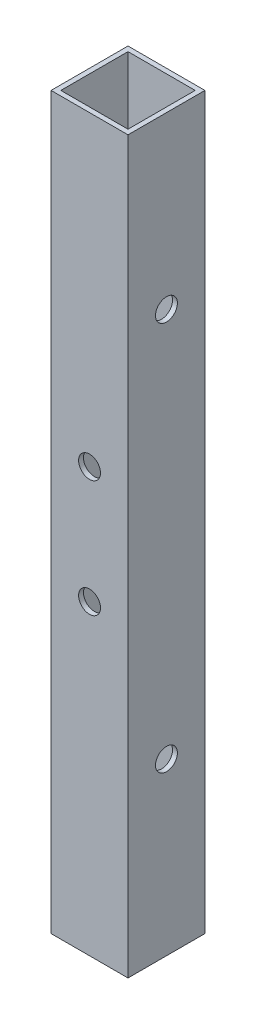
SolidWorks part; units mm, degrees
ref_plane "Front Plane" through (0, 0, 0) normal (0, 0, 1) x (1, 0, 0)
ref_plane "Top Plane" through (0, 0, 0) normal (0, 1, 0) x (1, 0, 0)
ref_plane "Right Plane" through (0, 0, 0) normal (1, 0, 0) x (0, 0, -1)
sketch "Sketch1" plane through (0, 0, 0) normal (0, 1, 0) x (1, 0, 0)
  line L0 (-6.9, -6.9) -> (-6.9, 6.9)
  line L1 (-7.9, -7.9) -> (7.9, -7.9)
  line L2 (-7.9, -7.9) -> (-7.9, 7.9)
  line L3 (-7.9, 7.9) -> (7.9, 7.9)
  line L4 (7.9, -7.9) -> (7.9, 7.9)
  line L5 (-7.9, -7.9) -> (7.9, 7.9) construction
  line L6 (-7.9, 7.9) -> (7.9, -7.9) construction
  line L7 (-6.9, 6.9) -> (6.9, 6.9)
  line L8 (6.9, -6.9) -> (6.9, 6.9)
  line L9 (-6.9, -6.9) -> (6.9, -6.9)
  point P0 (0, 0)
  dimension "D1" = 1
extrude "Boss-Extrude1" add sketch "Sketch1" along normal blind 150
sketch "Sketch2" plane through (-7.9, 0, 0) normal (-1, 0, 0) x (0, 0, 1)
  circle A0 centre (0, 115) radius 2.25
  circle A2 centre (0, 35) radius 2.25
  dimension "D1" = 4.5
  dimension "D2" = 80
  dimension "D3" = 4.5
extrude "Cut-Extrude1" cut sketch "Sketch2" against normal through all
sketch "Sketch3" plane through (0, 0, 7.9) normal (0, 0, 1) x (1, 0, 0)
  line L0 (7.9, 75) -> (-7.9, 75) construction
  line L1 (-7.9, 150) -> (-7.9, 0) construction
  circle A0 centre (0, 87) radius 2.25
  circle A1 centre (0, 63) radius 2.25
  point P5 (7.9, 75)
  dimension "D2" = 4.5
  dimension "D3" = 4.5
  dimension "D4" = 12
  dimension "D1" = 24
extrude "Cut-Extrude3" cut sketch "Sketch3" against normal through all
